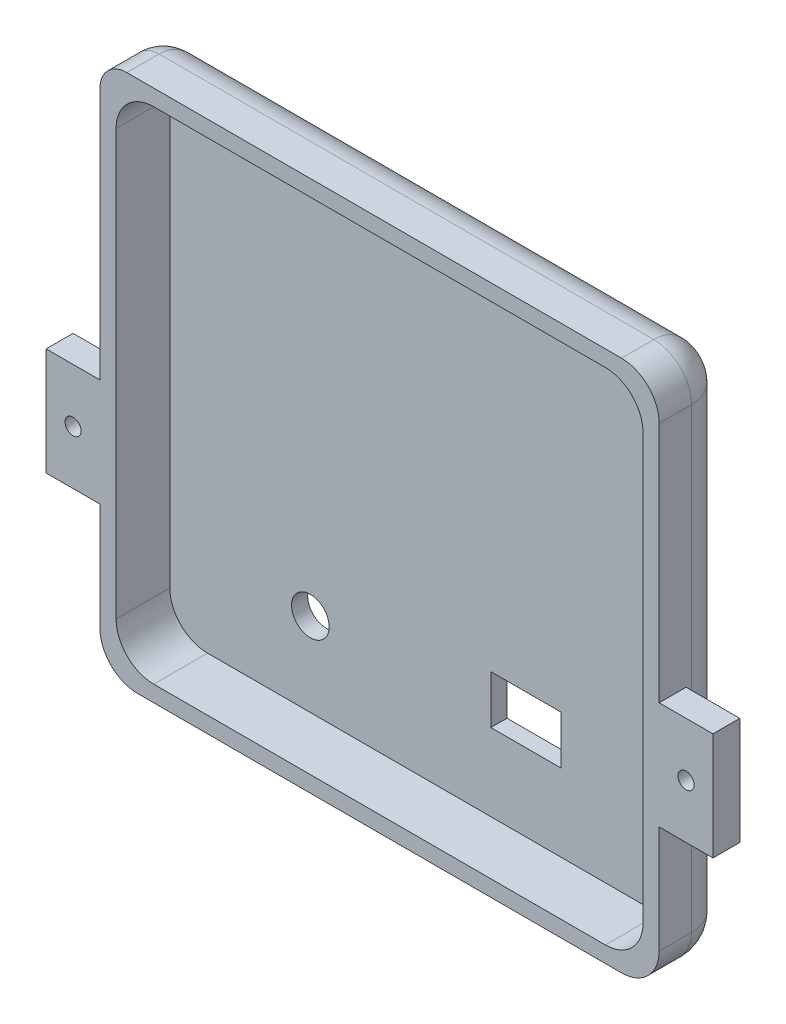
SolidWorks part; units mm, degrees
ref_plane "Front Plane" through (0, 0, 0) normal (0, 0, 1) x (1, 0, 0)
ref_plane "Top Plane" through (0, 0, 0) normal (0, 1, 0) x (1, 0, 0)
ref_plane "Right Plane" through (0, 0, 0) normal (1, 0, 0) x (0, 0, -1)
sketch "Sketch1" plane through (0, 0, 0) normal (0, 0, 1) x (1, 0, 0)
  line L1 (-49.6629, 38.7079) -> (54.3371, 38.7079)
  line L2 (-49.6629, 38.7079) -> (-49.6629, -60.2921)
  line L3 (-49.6629, -60.2921) -> (54.3371, -60.2921)
  line L4 (54.3371, 38.7079) -> (54.3371, -60.2921)
  dimension "D1" = 104
  dimension "D2" = 99
extrude "Boss-Extrude1" add sketch "Sketch1" along normal blind 13
shell "Shell2" thickness 3 removed face at (2.3371, -10.7921, 13)
sketch "Sketch2" plane through (-49.6629, 0, -36.6629) normal (1, 0, 0) x (0, 0, -1)
  line L6 (54.3371, -60.2921) -> (54.3371, 38.7079)
sketch "Sketch3" plane through (-49.6629, 0, 0) normal (-1, 0, 0) x (0, 0, 1)
  line L0 (13, 38.7079) -> (13, -60.2921) construction
  line L1 (13, -33.2921) -> (8, -33.2921)
  line L2 (13, -33.2921) -> (13, -13.2921)
  line L3 (13, -13.2921) -> (8, -13.2921)
  line L4 (8, -33.2921) -> (8, -13.2921)
  line L5 (13, -60.2921) -> (0, -60.2921) construction
  dimension "D1" = 20
  dimension "D2" = 5
  dimension "D3" = 27
extrude "Boss-Extrude2" add sketch "Sketch3" along normal blind 10 contours L2 L1 L4 L3
sketch "Sketch4" plane through (0, 0, 13) normal (0, 0, 1) x (1, 0, 0)
  line L0 (54.3371, -60.2921) -> (54.3371, 38.7079) construction
  line L1 (54.3371, -33.2921) -> (64.3371, -33.2921)
  line L2 (54.3371, -33.2921) -> (54.3371, -13.2921)
  line L3 (54.3371, -13.2921) -> (64.3371, -13.2921)
  line L4 (64.3371, -33.2921) -> (64.3371, -13.2921)
  line L5 (-49.6629, -60.2921) -> (54.3371, -60.2921) construction
  dimension "D1" = 10
  dimension "D2" = 20
  dimension "D3" = 27
extrude "Boss-Extrude3" add sketch "Sketch4" against normal blind 5 contours L2 L1 L4 L3
sketch "Sketch5" plane through (0, 0, 13) normal (0, 0, 1) x (1, 0, 0)
  line L0 (-54.6629, -39.2551) -> (-54.6629, -3.1965) construction
  line L1 (-59.6629, -33.2921) -> (-59.6629, -13.2921) construction
  line L2 (-77.1255, -23.2921) -> (77.4592, -23.2921) construction
  line L3 (-49.6629, -60.2921) -> (54.3371, -60.2921) construction
  line L4 (-59.6629, -33.2921) -> (-49.6629, -33.2921) construction
  line L5 (59.3371, -40.2567) -> (59.3371, -8.8723) construction
  line L6 (64.3371, -33.2921) -> (64.3371, -13.2921) construction
  circle A0 centre (59.3371, -23.2921) radius 1.5
  circle A1 centre (-54.6629, -23.2921) radius 1.5
  dimension "D1" = 5
  dimension "D2" = 37
  dimension "D3" = 10
  dimension "D4" = 5
extrude "Cut-Extrude1" cut sketch "Sketch5" against normal blind 5
fillet "Fillet2" radius 7 1 edges at (51.3371, -57.2921, 8)
fillet "Fillet3" radius 7 1 edges at (-46.6629, -57.2921, 8)
fillet "Fillet4" radius 7 1 edges at (51.3371, 35.7079, 8)
fillet "Fillet5" radius 7 1 edges at (-46.6629, 35.7079, 8)
fillet "Fillet6" radius 7 1 edges at (54.3371, -60.2921, 6.5)
fillet "Fillet7" radius 7 1 edges at (-49.6629, -60.2921, 6.5)
fillet "Fillet8" radius 7 1 edges at (54.3371, 38.7079, 6.5)
fillet "Fillet9" radius 5 1 edges at (-49.6629, 38.7079, 6.5)
fillet "Fillet10" radius 7 8 edges at (-47.6127, -58.2419, 0) (-49.6629, -9.7921, 0) (-48.1985, 37.2434, 0) (1.3371, 38.7079, 0) (52.2868, 36.6576, 0) (54.3371, -10.7921, 0) (52.2868, -58.2419, 0) (2.3371, -60.2921, 0)
sketch "Sketch6" plane through (64.3371, 0, 0) normal (1, 0, 0) x (0, 0, -1)
sketch "Sketch9" plane through (0, 0, 0) normal (0, 0, -1) x (-1, 0, 0)
  circle A0 centre (20.5334, -41.7592) radius 3.5
extrude "Cut-Extrude4" cut sketch "Sketch9" against normal blind 10
sketch "Sketch10" plane through (0, 0, 0) normal (0, 0, -1) x (-1, 0, 0)
  line L1 (-13.0423, -42.9277) -> (-26.0423, -42.9277)
  line L2 (-13.0423, -42.9277) -> (-13.0423, -33.9277)
  line L3 (-13.0423, -33.9277) -> (-26.0423, -33.9277)
  line L4 (-26.0423, -42.9277) -> (-26.0423, -33.9277)
  point P4 (-19.5423, -42.9277)
  dimension "D1" = 9
  dimension "D2" = 13
extrude "Cut-Extrude5" cut sketch "Sketch10" against normal blind 10
